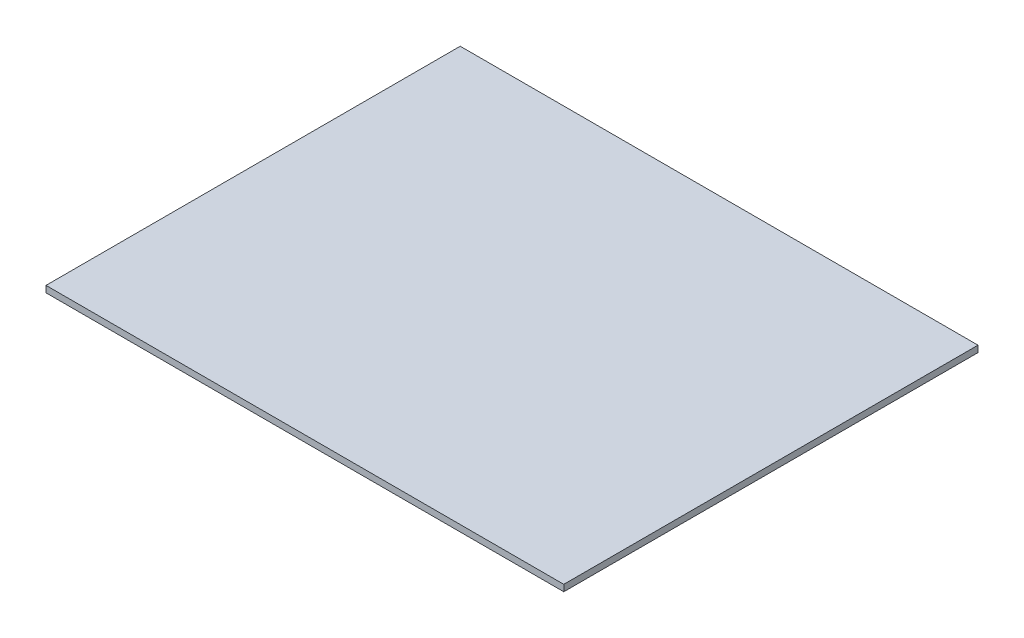
SolidWorks part; units mm, degrees
material "6061 Alloy"
ref_plane "Front Plane" through (0, 0, 0) normal (0, 0, 1) x (1, 0, 0)
ref_plane "Top Plane" through (0, 0, 0) normal (0, 1, 0) x (1, 0, 0)
ref_plane "Right Plane" through (0, 0, 0) normal (1, 0, 0) x (0, 0, -1)
sketch "Sketch1" plane through (0, 0, 0) normal (0, 1, 0) x (1, 0, 0)
  line L1 (-190.5, -152.4) -> (190.5, -152.4)
  line L2 (-190.5, -152.4) -> (-190.5, 152.4)
  line L3 (-190.5, 152.4) -> (190.5, 152.4)
  line L4 (190.5, -152.4) -> (190.5, 152.4)
  line L5 (-190.5, -152.4) -> (190.5, 152.4) construction
  line L6 (-190.5, 152.4) -> (190.5, -152.4) construction
  point P0 (0, 0)
  dimension "D1" = 304.8
  dimension "D2" = 381
extrude "Boss-Extrude1" add sketch "Sketch1" along normal blind 4.7625
